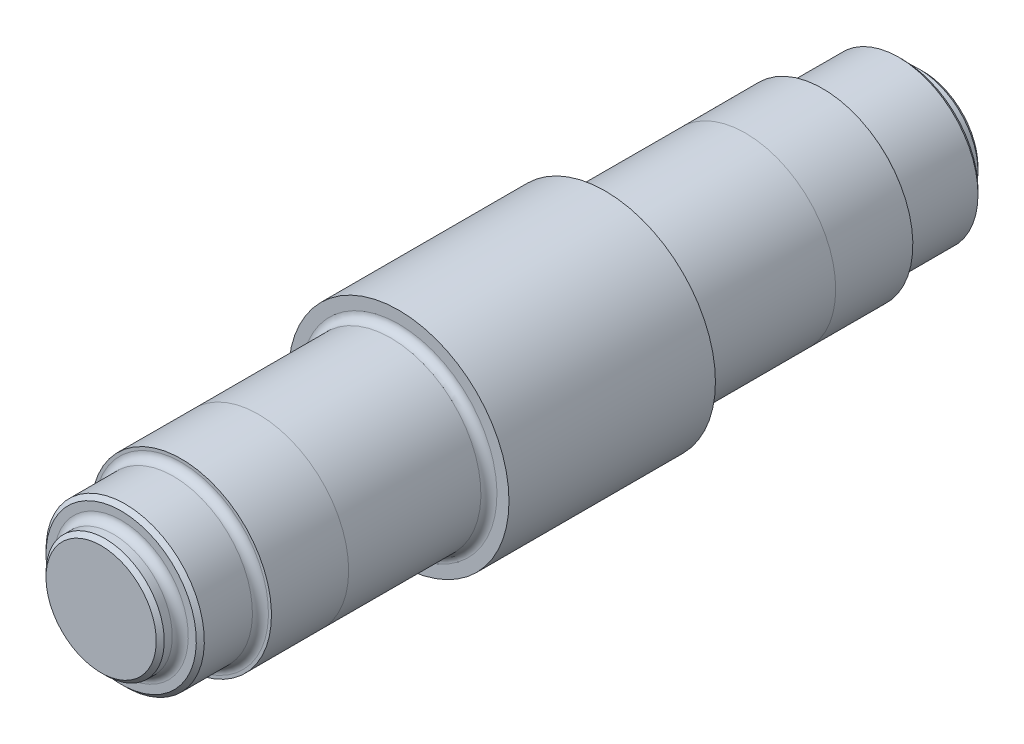
SolidWorks part; units mm, degrees
material "1.7225 (42CrMo4)"
ref_plane "前基準面" through (0, 0, 0) normal (0, 0, 1) x (1, 0, 0)
ref_plane "上基準面" through (0, 0, 0) normal (0, 1, 0) x (1, 0, 0)
ref_plane "右基準面" through (0, 0, 0) normal (1, 0, 0) x (0, 0, -1)
sketch "Sketch1" plane through (0, 0, 0) normal (1, 0, 0) x (0, 0, -1)
  line L0 (-21, 0) -> (21, 0) construction
  line L1 (0, -5.5) -> (0, 5.5) construction
  line L3 (5.15, 5.5) -> (5.15, 4.5)
  line L4 (5.15, 4.5) -> (15, 4.5)
  line L5 (-5.15, 5.5) -> (5.15, 5.5)
  line L6 (15, 4.5) -> (16, 4.5)
  line L7 (16, 4.5) -> (16, 3.95)
  line L9 (21, 0) -> (21, 3.95)
  line L16 (16, 3.95) -> (21, 3.95)
  line L18 (-16, 4.5) -> (-16, 3.95)
  line L19 (-15, 4.5) -> (-16, 4.5)
  line L20 (-5.15, 4.5) -> (-15, 4.5)
  line L21 (-5.15, 5.5) -> (-5.15, 4.5)
  line L23 (-16, 3.95) -> (-20, 3.95)
  line L24 (-20, 3.95) -> (-20, 0)
  line L25 (-20, 0) -> (21, 0)
  point P4 (0, 0)
  point P8 (0, 0)
  point P15 (0, 0)
  dimension "D1" = 15
  dimension "D2" = 9.85
  dimension "D3" = 9
  dimension "D4" = 11
  dimension "D5" = 1
  dimension "D6" = 5
  dimension "D7" = 3.95
  dimension "D8" = 4
revolve "Revolve1" add sketch "Sketch1" angle 360 about L25
fillet "bearingBoreFillet" radius 0.4 2 edges at (0, -4.5, 5.15) (0, -4.5, -5.15)
fillet "Fillet2" radius 0.4 2 edges at (0, -3.95, -16) (0, -3.95, 16)
sketch "Sketch2" plane through (0, 0, 0) normal (0, 0, 1) x (1, 0, 0)
  circle A0 centre (0, 0) radius 2.95
  dimension "D1" = 5.9
extrude "Cut-Extrude1" cut sketch "Sketch2" against normal blind 1 from surface flip side to cut starting at face at (0, -3.95, 20)
extrude "Cut-Extrude2" cut sketch "Sketch2<2>" along normal blind 1 from surface flip side to cut starting at face at (0, -3.95, -21)
sketch "Sketch2<2>" plane through (0, 0, 0) normal (0, 0, 1) x (1, 0, 0) same geometry as "Sketch2"
fillet "Fillet3" radius 0.4 2 edges at (0, 2.95, 19) (0, -2.95, -20)
chamfer "Chamfer1" distance 0.2 angle 45 4 edges at (0, -2.95, -21) (0, 3.95, -20) (0, 2.95, 20) (0, 3.95, 19)
sketch "Sketch3" plane through (0, 0, 0) normal (1, 0, 0) x (0, 0, -1)
  line L0 (12.15, 4.5) -> (12.15, -4.5)
  line L1 (16, 4.5) -> (5.55, 4.5) construction
  line L2 (5.55, -4.5) -> (16, -4.5) construction
  line L3 (-12.15, -4.5) -> (-12.15, 4.5)
  line L4 (-16, -4.5) -> (-5.55, -4.5) construction
  line L5 (-5.55, 4.5) -> (-16, 4.5) construction
  line L6 (5.15, -5.5) -> (5.15, 5.5) construction
  line L7 (-5.15, 4.9) -> (-5.15, -4.9) construction
  dimension "D1" = 7
  dimension "D2" = 7
split line "Split Line1"
